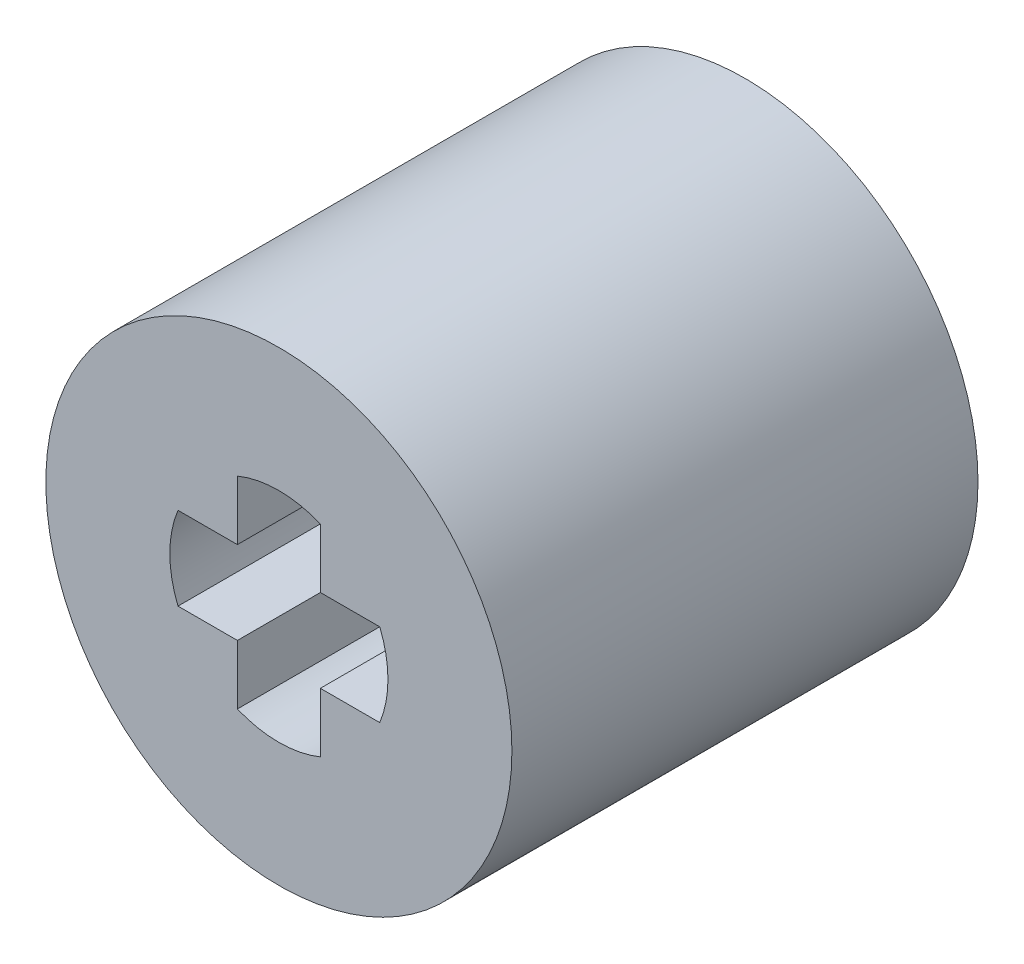
SolidWorks part; units mm, degrees
ref_plane "Front Plane" through (0, 0, 0) normal (0, 0, 1) x (1, 0, 0)
ref_plane "Top Plane" through (0, 0, 0) normal (0, 1, 0) x (1, 0, 0)
ref_plane "Right Plane" through (0, 0, 0) normal (1, 0, 0) x (0, 0, -1)
sketch "Sketch1" plane through (0, 0, 0) normal (0, 0, 1) x (1, 0, 0)
  line L0 (-0.89, 2.1641) -> (-0.89, -2.1641)
  line L2 (0.89, -2.1641) -> (0.89, 2.1641)
  line L4 (-1.118, 1) -> (1.118, 1)
  line L5 (-2.1641, 0.89) -> (2.1641, 0.89)
  line L7 (-2.1641, -0.89) -> (2.1641, -0.89)
  circle A0 centre (0, 0) radius 2.34
  circle A1 centre (0, 0) radius 1.5
  circle A2 centre (0, 0) radius 5
  dimension "D1" = 4.68
  dimension "D3" = 3
  dimension "D8" = 10
  dimension "D2" = 1.78
  dimension "D4" = 1
  dimension "D5" = 1.78
  dimension "D6" = 0.89
  dimension "D7" = 0.89
extrude "Boss-Extrude1" add sketch "Sketch1" along normal blind 5 contours A2 A0 | A1 L0 A0 L5 | A1 L5 A0 L2 | L4 A1 L5 L0 | L0 A1 L4 | L4 A1 L2 | L5 A1 L4 L2 | L2 A1 L7 | A1 L2 A0 L7 | A1 L7 A0 L0 | L7 A1 L0 region at (-1.3916, 1.3916, 0) region at (-0.9686, 1.0715, 0) region at (1.3916, 1.3916, 0) region at (-1.0283, 0.942, 0) region at (0.9686, 1.0715, 0) region at (-1.3916, -1.3916, 0) region at (1.0283, 0.942, 0) region at (-1.0011, -1.0011, 0) region at (1.3916, -1.3916, 0) region at (1.0011, -1.0011, 0) region at (-4.8586, 0, 0)
extrude "Boss-Extrude2" add sketch "Sketch1<3>" against normal blind 5 contours A2 A0 | A1 L2 A0 L7 | A1 L7 A0 L5 | A1 L5 A0 L2 | A1 L2 A0 L0 | A1 L0 A0 L5 | A1 L5 A0 L7 | A1 L7 A0 L0 | L4 A1 L2 | L2 A1 L0 L4 | L0 A1 L4 | A1 L0 A0 L2 region at (0, 1.8418, 0) region at (-1.3916, 1.3916, 0) region at (0, 1.2124, 0) region at (-0.9686, 1.0715, 0) region at (1.3916, 1.3916, 0) region at (-1.8418, 0, 0) region at (0.9686, 1.0715, 0) region at (1.8418, 0, 0) region at (-1.3916, -1.3916, 0) region at (0, -1.8418, 0) region at (1.3916, -1.3916, 0) region at (-4.8586, 0, 0)
sketch "Sketch1<3>" plane through (0, 0, 0) normal (0, 0, 1) x (1, 0, 0) same geometry as "Sketch1"
